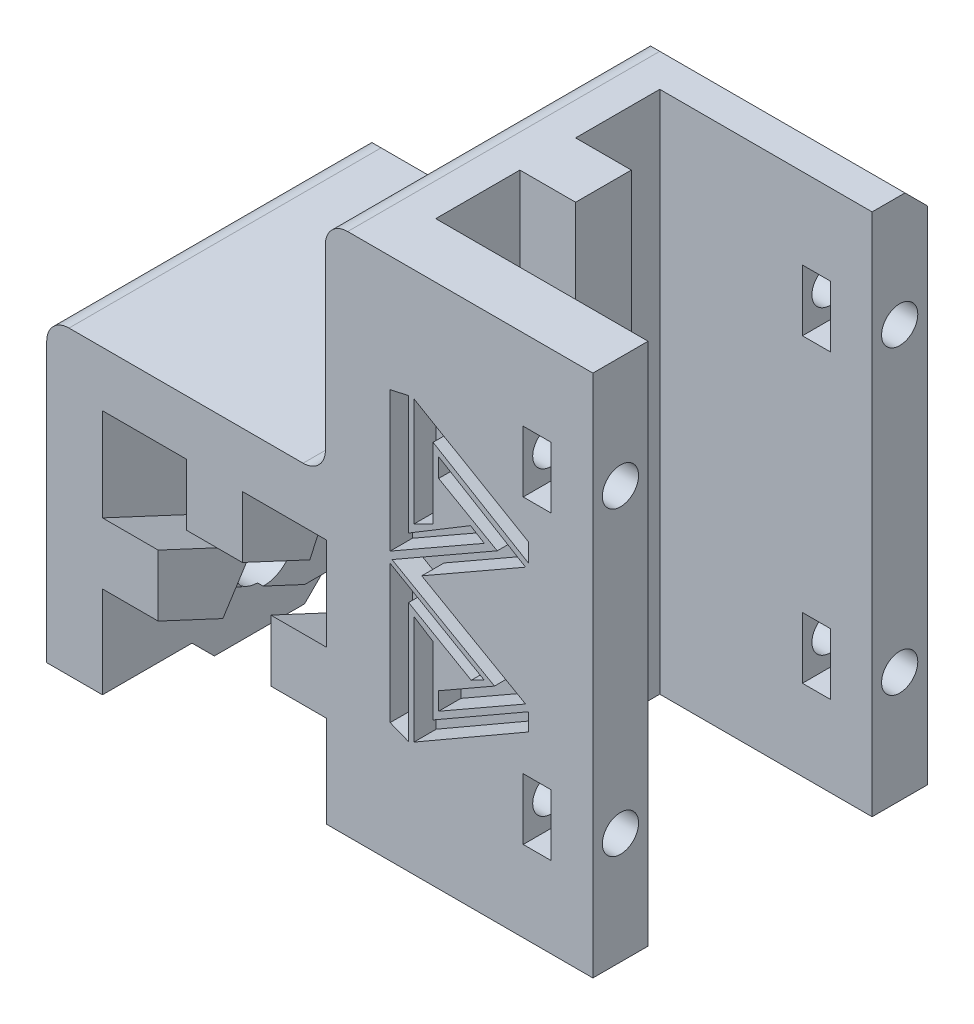
SolidWorks part; units mm, degrees
ref_plane "Front Plane" through (0, 0, 0) normal (0, 0, 1) x (1, 0, 0)
ref_plane "Top Plane" through (0, 0, 0) normal (0, 1, 0) x (1, 0, 0)
ref_plane "Right Plane" through (0, 0, 0) normal (1, 0, 0) x (0, 0, -1)
sketch "Sketch1" plane through (0, 0, 0) normal (0, 1, 0) x (1, 0, 0)
  line L1 (-15, -15) -> (15, -15)
  line L2 (-15, -15) -> (-15, 15)
  line L3 (-15, 15) -> (15, 15)
  line L4 (15, -15) -> (15, 15)
  line L5 (-15, -15) -> (15, 15) construction
  line L6 (-15, 15) -> (15, -15) construction
  point P0 (0, 0)
  dimension "D1" = 30
  dimension "D2" = 30
extrude "Boss-Extrude1" add sketch "Sketch1" along normal blind 50
sketch "Sketch2" plane through (0, 50, 0) normal (0, 1, 0) x (1, 0, 0)
  line L1 (-10.05, -10.05) -> (10.05, -10.05)
  line L2 (-10.05, -10.05) -> (-10.05, 10.05)
  line L3 (-10.05, 10.05) -> (10.05, 10.05)
  line L4 (10.05, -10.05) -> (10.05, 10.05)
  line L5 (-10.05, -10.05) -> (10.05, 10.05) construction
  line L6 (-10.05, 10.05) -> (10.05, -10.05) construction
  line L7 (-10.05, 0) -> (10.05, 0) construction
  line L8 (-10.05, 2.5) -> (-5.05, 2.5)
  line L9 (-5.05, 2.5) -> (-5.05, -2.5)
  line L10 (-5.05, -2.5) -> (-10.05, -2.5)
  point P0 (0, 0)
  dimension "D1" = 20.1
  dimension "D2" = 20.1
  dimension "D3" = 5
  dimension "D4" = 2.5
  dimension "D5" = 5
extrude "Cut-Extrude1" cut sketch "Sketch2" against normal through all contours L9 L10 L2 L1 L4 L3 L8 region at (0.498, 50, 0)
sketch "Sketch3" plane through (0, 50, 0) normal (0, 1, 0) x (1, 0, 0)
  line L0 (15, 15) -> (-15, 15) construction
  line L1 (9, 15) -> (15, 15)
  line L2 (9, 15) -> (9, -15)
  line L3 (9, -15) -> (15, -15)
  line L4 (15, 15) -> (15, -15)
  line L5 (-15, -15) -> (15, -15) construction
  dimension "D1" = 6
extrude "Cut-Extrude2" cut sketch "Sketch3" against normal through all
sketch "Sketch5" plane through (-15, 0, 0) normal (-1, 0, 0) x (0, 0, 1)
  line L1 (-15, 30) -> (15, 30)
  line L2 (-15, 30) -> (-15, 0)
  line L3 (-15, 0) -> (15, 0)
  line L4 (15, 30) -> (15, 0)
extrude "Boss-Extrude2" add sketch "Sketch5" along normal blind 25
sketch "Sketch6" plane through (-40, 0, 0) normal (-1, 0, 0) x (0, 0, 1)
  line L0 (-23.4514, 12.0698) -> (15, 30) construction
  line L1 (15, 0) -> (15, 30) construction
  dimension "D1" = 65
ref_plane "45 Angle plane" through (-40, 12.0698, -23.4514) normal (0, -0.4226, -0.9063) x (-1, 0, 0)
sketch "Sketch7" plane through (-40, 12.0698, -23.4514) normal (0, -0.4226, -0.9063) x (-1, 0, 0)
  line L0 (-49, -14.5107) -> (0, -14.5107) construction
  line L1 (-25.1, -24.5607) -> (-5, -24.5607)
  line L2 (-25.1, -24.5607) -> (-25.1, -4.4607)
  line L3 (-25.1, -4.4607) -> (-5, -4.4607)
  line L4 (-5, -24.5607) -> (-5, -4.4607)
  line L5 (-25.1, -24.5607) -> (-5, -4.4607) construction
  line L6 (-25.1, -4.4607) -> (-5, -24.5607) construction
  line L7 (0, -14.5107) -> (0, -27.1892) construction
  line L8 (-15.05, -4.4607) -> (-15.05, -24.5607) construction
  line L9 (-25.1, -14.5107) -> (-5, -14.5107)
  line L10 (-12.55, -4.4607) -> (-12.55, -9.4607)
  line L11 (-12.55, -9.4607) -> (-17.55, -9.4607)
  line L12 (-17.55, -9.4607) -> (-17.55, -4.4607)
  line L13 (-25.1, -12.0107) -> (-20.1, -12.0107)
  line L14 (-20.1, -12.0107) -> (-20.1, -17.0107)
  line L15 (-20.1, -17.0107) -> (-25.1, -17.0107)
  line L16 (-12.55, -24.5607) -> (-12.55, -19.5607)
  line L17 (-12.55, -19.5607) -> (-17.55, -19.5607)
  line L18 (-17.55, -19.5607) -> (-17.55, -24.5607)
  line L19 (-5, -12.0107) -> (-10, -12.0107)
  line L20 (-10, -12.0107) -> (-10, -17.0107)
  line L21 (-10, -17.0107) -> (-5, -17.0107)
  point P0 (-15.05, -14.5107)
  dimension "D1" = 20.1
  dimension "D2" = 20.1
  dimension "D3" = 5
  dimension "D4" = 5
  dimension "D5" = 2.5
  dimension "D6" = 5
  dimension "D7" = 5
  dimension "D8" = 5
  dimension "D9" = 2.5
extrude "45 degree extrusion cut" cut sketch "Sketch7" against normal through all contours L21 L20 L9 L14 L15 L2 L1 L18 L17 L16 L4 | L20 L19 L4 L3 L10 L11 L12 L2 L13 L14 L9 region at (-15.1247, -6.7684, -14.667) region at (-15.1247, 4.6058, -19.9708)
sketch "Sketch11" plane through (9, 0, 0) normal (1, 0, 0) x (0, 0, -1)
  line L0 (12.525, 50) -> (12.525, 40) construction
  line L1 (15, 50) -> (10.05, 50) construction
  line L2 (12.525, 0) -> (12.525, 13) construction
  line L3 (15, 0) -> (10.05, 0) construction
  line L4 (-12.525, 0) -> (-12.525, 13) construction
  line L5 (-10.05, 0) -> (-15, 0) construction
  line L6 (-12.525, 50) -> (-12.525, 40) construction
  line L7 (-10.05, 50) -> (-15, 50) construction
  circle A0 centre (-12.525, 40) radius 1.625
  circle A1 centre (12.525, 40) radius 1.625
  circle A2 centre (12.525, 13) radius 1.625
  circle A3 centre (-12.525, 13) radius 1.625
  dimension "D5" = 3.25
  dimension "D6" = 3.25
  dimension "D7" = 3.25
  dimension "D8" = 3.25
  dimension "D1" = 10
  dimension "D2" = 10
  dimension "D3" = 13
  dimension "D4" = 13
extrude "Cut-Extrude7" cut sketch "Sketch11" against normal blind 10
chamfer "Chamfer1" distance 2 angle 45 6 edges at (-5.45, 0, -15) (-35, 0, -15) (-3, 50, -15) (-40, 15, -15)
fillet "Fillet1" radius 2 4 edges at (-15, 50, 1) (-40, 30, 1) (-40, 0, 1)
sketch "Sketch16" plane through (-40, 0, 0) normal (-1, 0, 0) x (0, 0, 1)
  line L0 (15, 13.9434) -> (-13, 0.8868) construction
  line L1 (15, 2) -> (15, 28) construction
  line L2 (-13, 28) -> (-13, 2) construction
  line L3 (-23.4514, 12.0698) -> (15, 30) construction
  circle A0 centre (1, 7.4151) radius 2.675
  dimension "D1" = 5.35
extrude "Cut-Extrude10" cut sketch "Sketch16" against normal blind 10
ref_plane "Plane1" through (-25, 0, 0) normal (-1, 0, 0) x (0, 0, 1)
sketch "Sketch18" plane through (-25, 0, 0) normal (-1, 0, 0) x (0, 0, 1)
  line L0 (14.8471, 13.729) -> (1, 7.4151) construction
  line L4 (9.9507, 7.3478) -> (5.6064, 14.1277)
  line L5 (9.9507, 7.3478) -> (-3.6064, 0.7025)
  line L6 (5.6064, 14.1277) -> (-7.9507, 7.4825)
  line L7 (-3.6064, 0.7025) -> (-7.9507, 7.4825)
  dimension "D1" = 8
  dimension "D2" = 15
  dimension "D3" = 7.5
  dimension "D4" = 4
extrude "Cut-Extrude11" cut sketch "Sketch18" against normal mid plane 19
fillet "Fillet2" radius 0.5 1 edges at (-24.95, 0, -3.0507)
fillet "Fillet3" radius 0.5 1 edges at (-24.95, 8.4172, 15)
sketch "Sketch19" plane through (0, 0, 15) normal (0, 0, 1) x (1, 0, 0)
  line L0 (-40, 2) -> (-40, 28) construction
  line L1 (-40, 3) -> (9, 3)
  line L2 (-40, 3) -> (-40, 0)
  line L3 (-40, 0) -> (9, 0)
  line L4 (9, 3) -> (9, 0)
  dimension "D1" = 3
extrude "Cut-Extrude12" cut sketch "Sketch19" against normal through all
sketch "Sketch20" plane through (0, 0, 15) normal (0, 0, 1) x (1, 0, 0)
  line L1 (-28.5785, 8.4284) -> (-21.8248, 8.4284)
  line L2 (-28.5785, 8.4284) -> (-28.5785, 2.1753)
  line L3 (-28.5785, 2.1753) -> (-21.8248, 2.1753)
  line L4 (-21.8248, 8.4284) -> (-21.8248, 2.1753)
extrude "Cut-Extrude13" cut sketch "Sketch20" against normal blind 15
sketch "Sketch21" plane through (-25, 0, 0) normal (-1, 0, 0) x (0, 0, 1)
  line L0 (-7.6246, 31.9083) -> (1.6243, 14.3185) construction
ref_plane "Plane2" through (-25, 31.9083, -7.6246) normal (0, 0.8851, -0.4654) x (1, 0, 0)
sketch "Sketch22" plane through (-25, 31.9083, -7.6246) normal (0, 0.8851, -0.4654) x (1, 0, 0)
  circle A0 centre (0.022, 0.0143) radius 2.65
  dimension "D1" = 5.3
extrude "Cut-Extrude14" cut sketch "Sketch22" against normal through all
sketch "Sketch23" plane through (-25, 31.9083, -7.6246) normal (0, 0.8851, -0.4654) x (1, 0, 0)
  circle A0 centre (0.022, 0.0143) radius 5
  dimension "D1" = 10
extrude "Cut-Extrude15" cut sketch "Sketch23" against normal blind 2.5
sketch "Sketch24" plane through (0, 10.3222, -4.8133) normal (0, -0.9063, 0.4226) x (1, 0, 0)
  line L0 (-27.45, 21.8616) -> (-27.45, 8.5079) construction
  line L1 (-27.45, 15.1847) -> (-22.45, 15.1847)
  line L2 (-27.45, 15.1847) -> (-27.45, 0.1847)
  line L3 (-27.45, 0.1847) -> (-22.45, 0.1847)
  line L4 (-22.45, 15.1847) -> (-22.45, 0.1847)
  line L5 (-22.45, 6.7563) -> (-22.45, -11.2398) construction
  dimension "D1" = 15
extrude "Cut-Extrude16" cut sketch "Sketch24" against normal blind 4
sketch "Sketch25" plane through (0, 3, 0) normal (0, -1, 0) x (1, 0, 0)
  line L0 (-40, -23.4514) -> (-40, 15) construction
  line L1 (-40, 6.9649) -> (-35, 6.9649)
  line L2 (-40, 6.9649) -> (-40, -5.1295)
  line L3 (-40, -5.1295) -> (-35, -5.1295)
  line L4 (-35, 6.9649) -> (-35, -5.1295)
  line L5 (-35, 15) -> (-35, -2.651) construction
extrude "Boss-Extrude3" add sketch "Sketch25" along normal blind 2
chamfer "Chamfer2" distance 2 angle 45 2 edges at (-37.5, 1, -5.1295) (-37.5, 1, 6.9649)
sketch "Sketch26" plane through (0, 0, 15) normal (0, 0, 1) x (1, 0, 0)
  line L0 (4, 50) -> (4, 40) construction
  line L1 (-13, 50) -> (9, 50) construction
  line L2 (4, 3) -> (4, 13) construction
  line L3 (9, 3) -> (-14.9, 3) construction
  line L4 (9, 3) -> (9, 50) construction
  line L6 (2.75, 37.25) -> (5.25, 37.25)
  line L7 (2.75, 37.25) -> (2.75, 42.75)
  line L8 (2.75, 42.75) -> (5.25, 42.75)
  line L9 (5.25, 37.25) -> (5.25, 42.75)
  line L10 (2.75, 37.25) -> (5.25, 42.75) construction
  line L11 (2.75, 42.75) -> (5.25, 37.25) construction
  line L12 (2.75, 10.25) -> (5.25, 10.25)
  line L13 (2.75, 10.25) -> (2.75, 15.75)
  line L14 (2.75, 15.75) -> (5.25, 15.75)
  line L15 (5.25, 10.25) -> (5.25, 15.75)
  line L16 (2.75, 10.25) -> (5.25, 15.75) construction
  line L17 (2.75, 15.75) -> (5.25, 10.25) construction
  dimension "D1" = 10
  dimension "D2" = 5
  dimension "D3" = 10
  dimension "D4" = 5
  dimension "D5" = 5.5
  dimension "D6" = 2.5
  dimension "D7" = 2.5
  dimension "D8" = 5.5
extrude "Cut-Extrude17" cut sketch "Sketch26" against normal through all
fillet "Fillet4" radius 0.5 3 edges at (-24.95, 5.5721, -15) (-32.5, 3, -14.482) (-17.4, 3, -14.482)
sketch "Mobious Logo" plane through (0, 0, 15) normal (0, 0, 1) x (-1, 0, 0)
  line L0 (-3.2109, -32.3487) -> (-3.2109, -34.0037)
  line L1 (-3.2109, -34.0037) -> (7.0562, -39.9788)
  line L2 (7.0562, -39.9788) -> (7.0562, -30.2448)
  line L3 (7.0562, -30.2448) -> (5.3383, -31.1222)
  line L4 (5.3383, -31.1222) -> (5.3383, -37.4541)
  line L5 (5.3383, -37.4541) -> (-3.2109, -32.3487)
  line L6 (1.9787, -32.6572) -> (0.7445, -31.8998)
  line L7 (0.7445, -31.8998) -> (9.1881, -27.0749)
  line L8 (9.1881, -27.0749) -> (9.1881, -39.6141)
  line L9 (9.1881, -39.6141) -> (7.533, -39.9851)
  line L10 (7.533, -39.9851) -> (7.533, -29.3079)
  line L11 (7.533, -29.3079) -> (1.9787, -32.6572)
  line L12 (4.84, -36.5845) -> (-2.9584, -31.8998)
  line L13 (-2.9584, -31.8998) -> (6.3555, -26.5699)
  line L14 (6.3555, -26.5699) -> (-2.9584, -21.2681)
  line L15 (-2.9584, -21.2681) -> (4.84, -16.8055)
  line L16 (4.84, -16.8055) -> (4.84, -18.4002)
  line L17 (4.84, -18.4002) -> (-0.1715, -21.2681)
  line L18 (-0.1715, -21.2681) -> (9.0195, -26.5)
  line L19 (9.0195, -26.5) -> (-0.4166, -31.8998)
  line L20 (-0.4166, -31.8998) -> (4.84, -34.8921)
  line L21 (4.84, -34.8921) -> (4.84, -36.5845)
  line L22 (-3.2109, -20.7912) -> (-3.2109, -19.2203)
  line L23 (-3.2109, -19.2203) -> (7.0562, -13.3014)
  line L24 (7.0562, -13.3014) -> (7.0562, -23.0634)
  line L25 (7.0562, -23.0634) -> (5.3383, -21.9694)
  line L26 (5.3383, -21.9694) -> (5.3383, -15.8821)
  line L27 (5.3383, -15.8821) -> (-3.2109, -20.7912)
  line L28 (0.7445, -21.2681) -> (9.1881, -26.1211)
  line L29 (9.1881, -26.1211) -> (9.1881, -13.7502)
  line L30 (9.1881, -13.7502) -> (7.533, -13.0939)
  line L31 (7.533, -13.0939) -> (7.533, -23.905)
  line L32 (7.533, -23.905) -> (1.9157, -20.6765)
  line L33 (1.9157, -20.6765) -> (0.7445, -21.2681)
  line L34 (-9, -26.5) -> (14.8874, -26.5) construction
  line L35 (-9, -3) -> (-9, -50) construction
extrude "Cut-Extrude18" cut sketch "Mobious Logo" against normal blind 2
